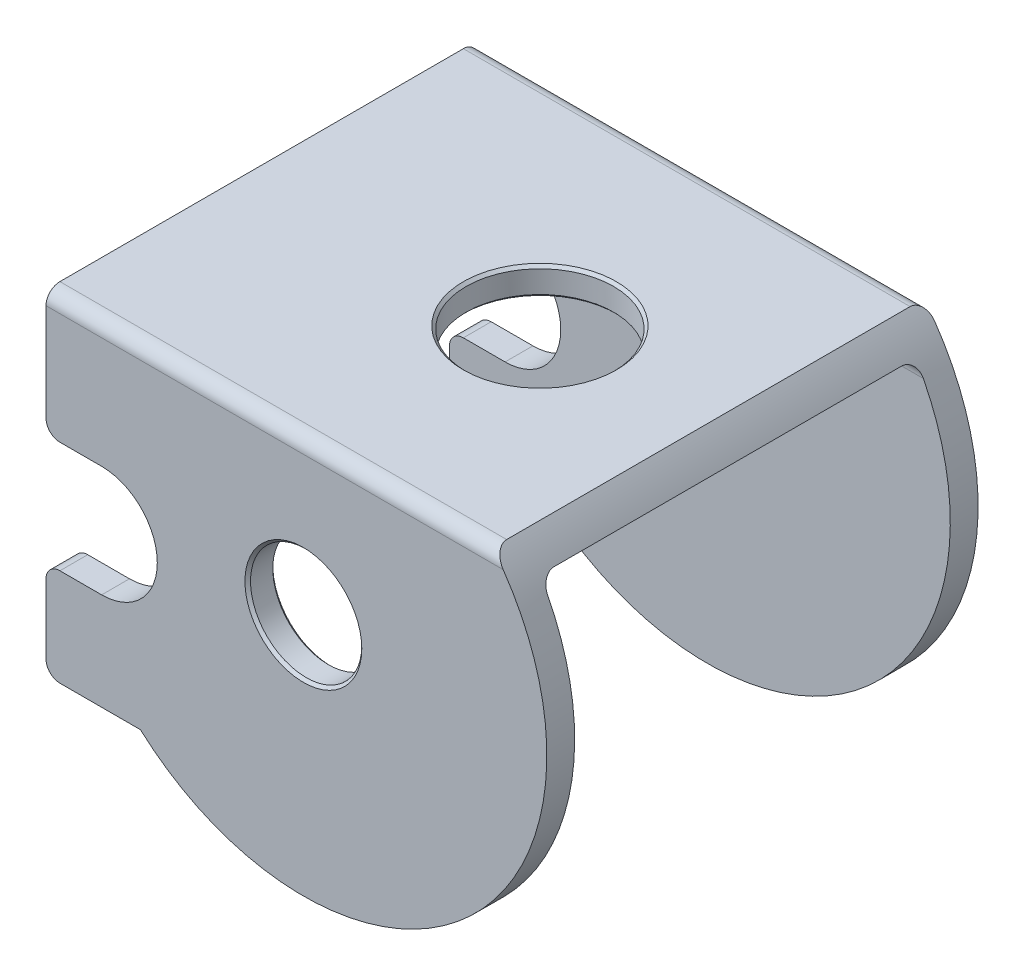
SolidWorks part; units mm, degrees
ref_plane "正面" through (0, 0, 0) normal (0, 0, 1) x (1, 0, 0)
ref_plane "平面" through (0, 0, 0) normal (0, 1, 0) x (1, 0, 0)
ref_plane "右側面" through (0, 0, 0) normal (1, 0, 0) x (0, 0, -1)
sketch "ｽｹｯﾁ1" plane through (0, 0, 0) normal (0, 0, 1) x (1, 0, 0)
  line L0 (-18.5, 11) -> (-18.5, -13)
  line L1 (-18.5, -13) -> (-11.7154, -13)
  line L2 (-18.5, 11) -> (13.6107, 11)
  arc A1 (-11.7154, -13) -> (13.6107, 11) centre (0, 0) ccw
  dimension "D4" = 11
  dimension "D3" = 18.5
  dimension "D2" = 35
  dimension "D1" = 24
extrude "GearA-W" add sketch "ｽｹｯﾁ1" along normal mid plane 31
sketch "ｽｹｯﾁ2" plane through (0, 0, 15.5) normal (0, 0, 1) x (1, 0, 0)
  line L0 (-18.5, 11) -> (-18.5, -13) construction
  line L1 (-18.5, 2) -> (-14.5, 2)
  line L2 (-18.5, 2) -> (-18.5, -6)
  line L3 (-18.5, -6) -> (-14.5, -6)
  line L5 (13.6107, 11) -> (-18.5, 11) construction
  arc A0 (-14.5, -6) -> (-14.5, 2) centre (-14.5, -2) ccw
  circle A1 centre (0, 0) radius 4
  dimension "D6" = 8
  dimension "D1" = 8
  dimension "D2" = 9
  dimension "D5" = 4
extrude "ｶｯﾄ - 押し出し1" cut sketch "ｽｹｯﾁ2" against normal through all
sketch "GearA-t" plane through (-18.5, 0, 0) normal (-1, 0, 0) x (0, 0, 1)
  line L14 (13.5, -17.5) -> (-13.5, -17.5)
  line L17 (-13.5, 9) -> (-13.5, -17.5)
  line L18 (13.5, 9) -> (-13.5, 9)
  line L19 (13.5, -17.5) -> (13.5, 9)
  line L20 (-13.5, 9) -> (-13.5, -17.5)
  line L21 (13.5, 9) -> (-13.5, 9)
  line L22 (13.5, -17.5) -> (13.5, 9)
  dimension "D1" = 2
extrude "ｶｯﾄ - 押し出し2" cut sketch "GearA-t" against normal through all
sketch "ｽｹｯﾁ4" plane through (0, 11, 0) normal (0, 1, 0) x (1, 0, 0)
  line L1 (-18.5, -15.5) -> (-18.5, 15.5) construction
  circle A0 centre (1.5, 0) radius 5.3
  dimension "D1" = 20
  dimension "D3" = 10.6
extrude "ｶｯﾄ - 押し出し3" cut sketch "ｽｹｯﾁ4" against normal up to next
fillet "ﾌｨﾚｯﾄ1" radius 1 6 edges at (-18.5, -13, -14.5) (-18.5, -13, 14.5) (-18.5, -6, -14.5) (-18.5, -6, 14.5) (-18.5, 2, -14.5) (-18.5, 2, 14.5)
fillet "ﾌｨﾚｯﾄ2" radius 1 4 edges at (-2.4447, 11, -15.5) (-2.4447, 11, 15.5) (-1.7458, 9, -13.5) (-1.7458, 9, 13.5)
chamfer "面取り1" distance 0.2 angle 45 6 edges at (4, 0, 15.5) (4, 0, -15.5) (1.5, 11, 5.3) (4, 0, 13.5) (-3.8, 9, 0) (0, 4, -13.5) tangent propagation no
